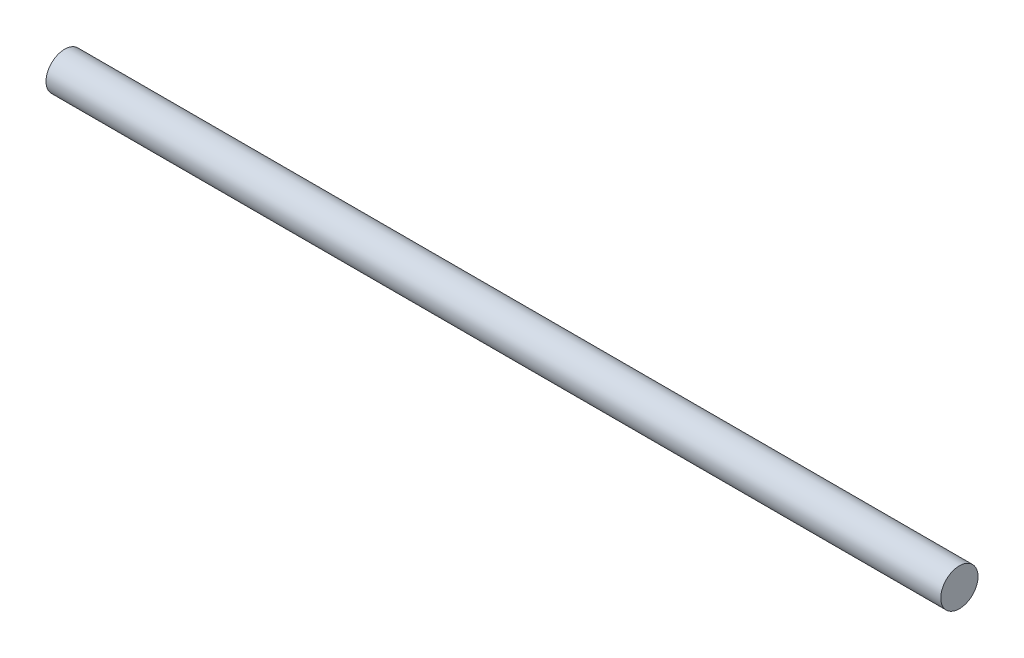
SolidWorks part; units mm, degrees
material "Cast Alloy Steel"
ref_plane "Front Plane" through (0, 0, 0) normal (0, 0, 1) x (1, 0, 0)
ref_plane "Top Plane" through (0, 0, 0) normal (0, 1, 0) x (1, 0, 0)
ref_plane "Right Plane" through (0, 0, 0) normal (1, 0, 0) x (0, 0, -1)
sketch "Sketch1" plane through (0, 0, 0) normal (1, 0, 0) x (0, 0, -1)
  circle A0 centre (0, 0) radius 6.35
  dimension "D1" = 12.7
extrude "Boss-Extrude1" add sketch "Sketch1" along normal blind 304.8
ref_plane "Plane1" through (152.4, 0, 0) normal (1, 0, 0) x (0, 0, -1)
